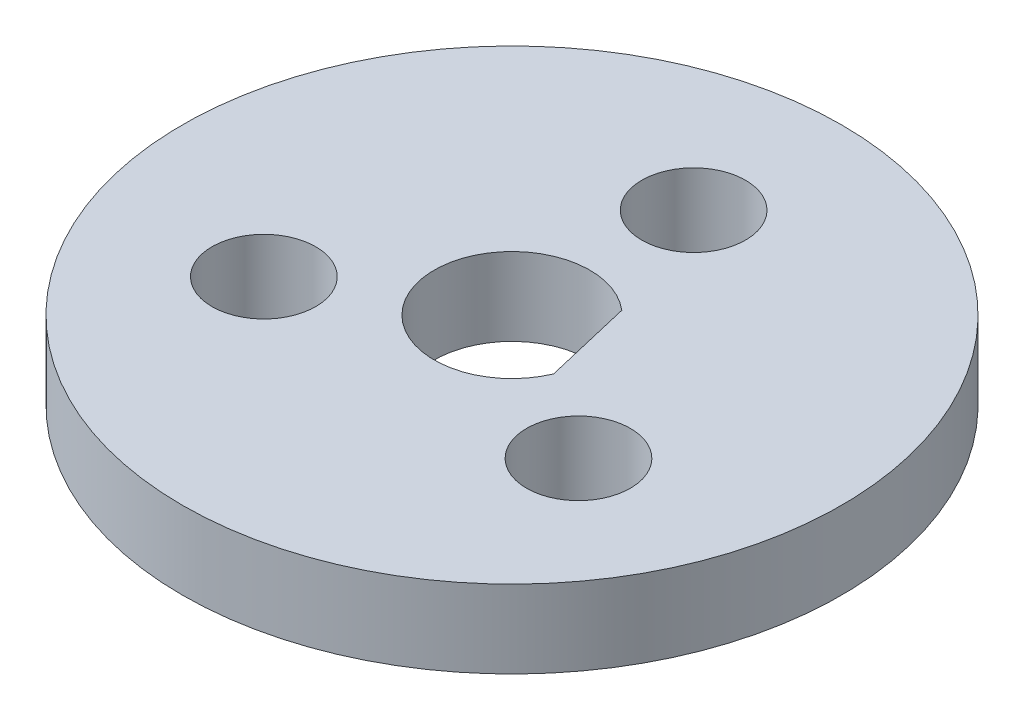
SolidWorks part; units mm, degrees
ref_plane "Front" through (0, 0, 0) normal (0, 0, 1) x (1, 0, 0)
ref_plane "Top" through (0, 0, 0) normal (0, 1, 0) x (1, 0, 0)
ref_plane "Right" through (0, 0, 0) normal (1, 0, 0) x (0, 0, -1)
sketch "Sketch1" plane through (0, 0, 0) normal (0, 1, 0) x (1, 0, 0)
  circle A0 centre (0, 0) radius 12.7
extrude "Boss-Extrude1" add sketch "Sketch1" along normal blind 3
sketch "Sketch2" plane through (0, 3, 0) normal (0, 1, 0) x (1, 0, 0)
  line L0 (1.9565, 2.2742) -> (2.7659, -1.1617)
  circle A0 centre (0, 0) radius 3
  dimension "D1" = 3.53
extrude "Cut-Extrude1" cut sketch "Sketch2" against normal blind 10 contours L0 A0 region at (-0.1327, 3, 0.0313)
sketch "Sketch3" plane through (0, 3, 0) normal (0, 1, 0) x (1, 0, 0)
  circle A0 centre (0, 0) radius 7
  circle A1 centre (0, 7) radius 2
  circle A2 centre (6.0622, -3.5) radius 2
  circle A3 centre (-6.0622, -3.5) radius 2
  point P11 (0, 0)
  dimension "D1" = 3
extrude "Cut-Extrude2" cut sketch "Sketch3" against normal blind 5 contours A1 | A3 | A2
